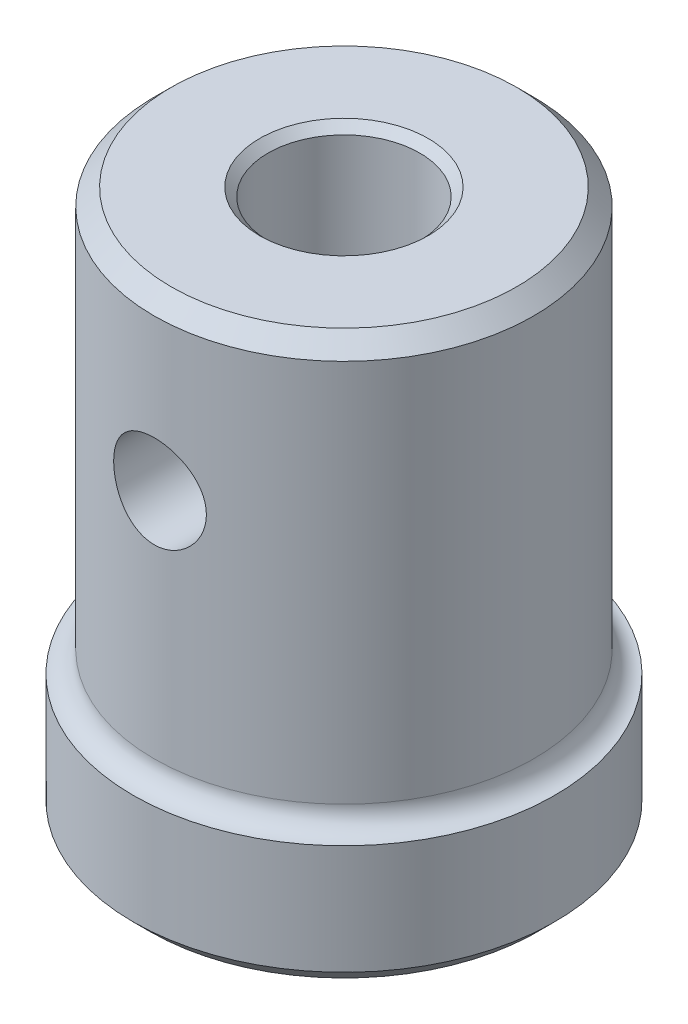
SolidWorks part; units mm, degrees
material "1.0060 (E335)"
ref_plane "Front Plane" through (0, 0, 0) normal (0, 0, 1) x (1, 0, 0)
ref_plane "Top Plane" through (0, 0, 0) normal (0, 1, 0) x (1, 0, 0)
ref_plane "Right Plane" through (0, 0, 0) normal (1, 0, 0) x (0, 0, -1)
sketch "Sketch1" plane through (0, 0, 0) normal (0, 1, 0) x (1, 0, 0)
  circle A0 centre (0, 0) radius 25
  dimension "D1" = 50
extrude "Boss-Extrude1" add sketch "Sketch1" along normal blind 15
sketch "Sketch2" plane through (0, 15, 0) normal (0, 1, 0) x (1, 0, 0)
  circle A0 centre (0, 0) radius 22.5
  dimension "D1" = 45
extrude "Boss-Extrude2" add sketch "Sketch2" along normal blind 50
sketch "Sketch3" plane through (0, 65, 0) normal (0, 1, 0) x (1, 0, 0)
  circle A0 centre (0, 0) radius 9
  dimension "D1" = 18
extrude "Cut-Extrude1" cut sketch "Sketch3" against normal blind 50
chamfer "Chamfer1" distance 2 angle 45 2 edges at (0, 65, 22.5) (0, 0, 25)
chamfer "Chamfer2" distance 1 angle 45 1 edges at (0, 65, 9)
fillet "Fillet1" radius 2.5 1 edges at (0, 15, 22.5)
sketch "Sketch4" plane through (0, 0, 0) normal (0, 0, 1) x (1, 0, 0)
  line L0 (0, -1000) -> (0, 49000) construction
  line L1 (0, 18) -> (-9, 18)
  line L2 (0, 15) -> (-9, 15)
  line L3 (0, 15) -> (0, 18)
  arc A0 (-9, 15) -> (-9, 18) centre (-9, 16.5) cw
  dimension "D1" = 3
  dimension "D2" = 18
  dimension "D3" = 15
revolve "Cut-Revolve1" cut sketch "Sketch4" angle 360 about L0
sketch "Sketch5" plane through (0, 0, 0) normal (0, 0, 1) x (1, 0, 0)
  line L0 (20.5, 65) -> (-20.5, 65) construction
  circle A0 centre (0, 45) radius 5.5
  point P2 (0, 41.2647)
  point P3 (0, 0)
  dimension "D1" = 11
  dimension "D2" = 20
extrude "Cut-Extrude2" cut sketch "Sketch5" against normal through all both and the other way through all
